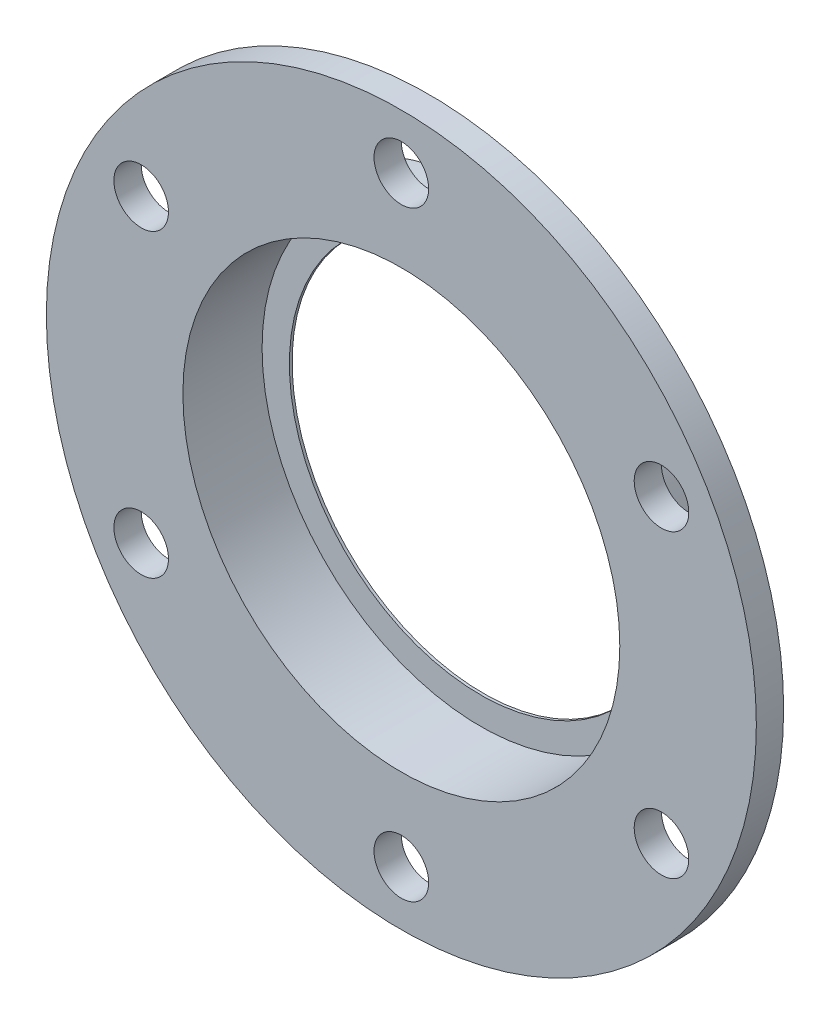
SolidWorks part; units mm, degrees
ref_plane "Front Plane" through (0, 0, 0) normal (0, 0, 1) x (1, 0, 0)
ref_plane "Top Plane" through (0, 0, 0) normal (0, 1, 0) x (1, 0, 0)
ref_plane "Right Plane" through (0, 0, 0) normal (1, 0, 0) x (0, 0, -1)
sketch "Sketch1" plane through (0, 0, 0) normal (0, 0, 1) x (1, 0, 0)
  circle A0 centre (0, 0) radius 45
  dimension "D1" = 90
extrude "Boss-Extrude1" add sketch "Sketch1" along normal blind 15
sketch "Sketch2" plane through (0, 0, 15) normal (0, 0, 1) x (1, 0, 0)
  circle A0 centre (0, 0) radius 40
  dimension "D1" = 80
extrude "Cut-Extrude1" cut sketch "Sketch2" against normal offset from surface (14.5 mm away) 0.5 up to face at (45, 0, 0)
sketch "Sketch3" plane through (0, 0, 0.5) normal (0, 0, 1) x (1, 0, 0)
  circle A0 centre (0, 0) radius 35
  dimension "D1" = 70
extrude "Cut-Extrude2" cut sketch "Sketch3" against normal through all
sketch "Sketch4" plane through (0, 0, 15) normal (0, 0, 1) x (1, 0, 0)
  circle A0 centre (0, 0) radius 65
  circle A1 centre (0, 0) radius 45
  circle A2 centre (0, 0) radius 45 construction
  dimension "D1" = 20
extrude "Boss-Extrude2" add sketch "Sketch4" against normal blind 5
sketch "Sketch5" plane through (0, 0, 10) normal (0, 0, -1) x (-1, 0, 0)
  circle A0 centre (0, 0) radius 55 construction
  circle A1 centre (0, 55) radius 5
  circle A2 centre (0, 0) radius 55 construction
  circle A3 centre (47.6314, 27.5) radius 5
  circle A4 centre (0, 0) radius 55 construction
  circle A5 centre (47.6314, -27.5) radius 5
  circle A6 centre (0, 0) radius 55 construction
  circle A7 centre (0, -55) radius 5
  circle A8 centre (0, 0) radius 55 construction
  circle A9 centre (-47.6314, -27.5) radius 5
  circle A10 centre (0, 0) radius 55 construction
  circle A11 centre (-47.6314, 27.5) radius 5
  point P23 (0, 0)
  dimension "D1" = 110
  dimension "D2" = 10
  dimension "D3" = 6
extrude "Cut-Extrude3" cut sketch "Sketch5" against normal through all
